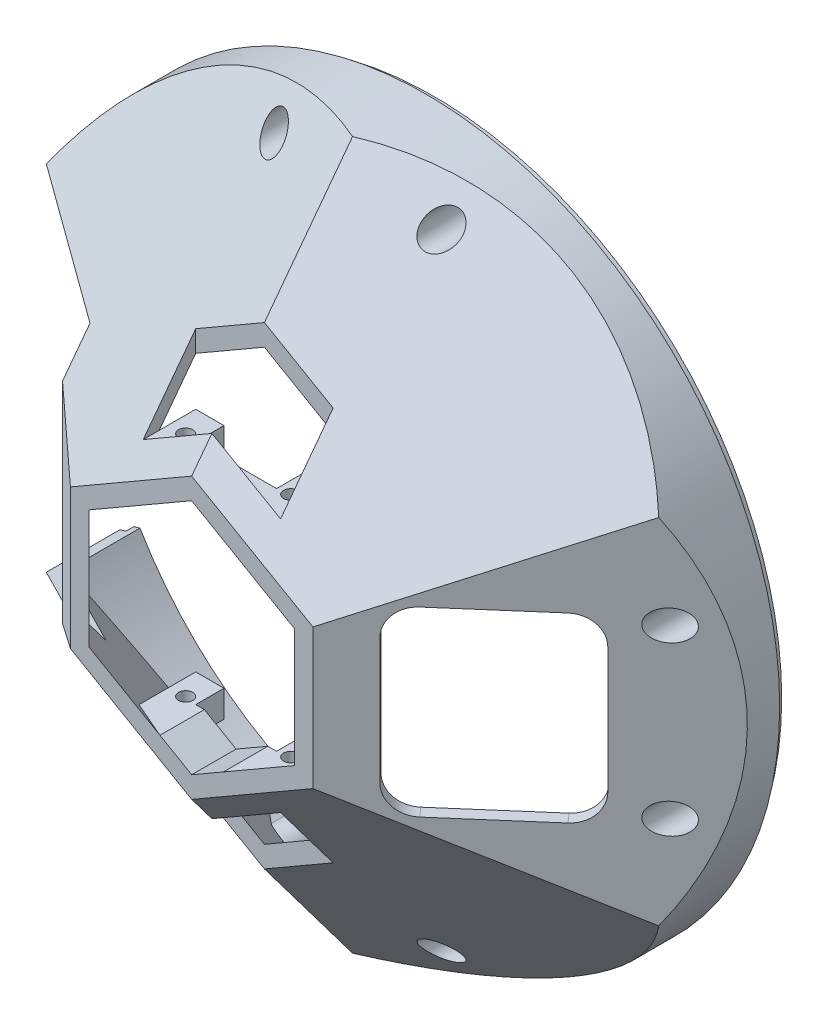
SolidWorks part; units mm, degrees
ref_plane "Front Plane" through (0, 0, 0) normal (0, 0, 1) x (1, 0, 0)
ref_plane "Top Plane" through (0, 0, 0) normal (0, 1, 0) x (1, 0, 0)
ref_plane "Right Plane" through (0, 0, 0) normal (1, 0, 0) x (0, 0, -1)
sketch "Sketch1" plane through (0, 0, 0) normal (0, 0, 1) x (1, 0, 0)
  circle A0 centre (0, 0) radius 87.5
  dimension "D1" = 175
extrude "Boss-Extrude1" add sketch "Sketch1" along normal blind 60
sketch "Sketch2" plane through (0, 0, 0) normal (0, 1, 0) x (1, 0, 0)
  line L0 (-73.4655, -109.9854) -> (-130.9655, -59.9854)
  line L1 (-73.4655, -109.9854) -> (-30, -60)
  line L2 (-130.9655, -59.9854) -> (-87.5, -10)
  line L3 (-30, -60) -> (-87.5, -10)
  line L4 (-73.4655, -109.9854) -> (-87.5, -10) construction
  line L5 (-130.9655, -59.9854) -> (-30, -60) construction
  line L7 (-87.5, 0) -> (-87.5, -60) construction
  line L8 (-87.5, -60) -> (87.5, -60) construction
  point P1 (-80.4828, -59.9927)
  dimension "D1" = 30
  dimension "D2" = 10
extrude "Cut-Extrude1" cut sketch "Sketch2" against normal through all and the other way through all
pattern_circular "CirPattern1" count 6 over 360 about axis through (0, 0, 0) along (0, 0, 1) of "Cut-Extrude1"
shell "Shell1" thickness 3 removed face at (87.5, 0, 0) removed face at (0, 0, 60)
sketch "Sketch3" plane through (0, 0, 0) normal (0, 0, -1) x (-1, 0, 0)
  circle A0 centre (0, 0) radius 87.5 construction
  circle A1 centre (0, 0) radius 87.5
  circle A2 centre (0, 0) radius 86
  dimension "D1" = 1.5
extrude "Cut-Extrude2" cut sketch "Sketch3" against normal blind 2
sketch "Sketch4" plane through (0, 0, 0) normal (0, 0, 1) x (1, 0, 0)
  line L8 (-45, 35) -> (-45, -35)
  line L9 (-30, -17.3205) -> (-30, 17.3205) construction
  line L10 (-75.7772, 43.75) -> (-45, 35)
  line L11 (-45, -35) -> (-75.7772, -43.75)
  line L12 (-45, 0) -> (0, 0) construction
  arc A1 (-75.7772, 43.75) -> (-75.7772, -43.75) centre (0, 0) ccw construction
  arc A2 (-75.7772, 43.75) -> (-75.7772, -43.75) centre (0, 0) ccw
  dimension "D1" = 15
  dimension "D2" = 70
extrude "Cut-Extrude3" cut sketch "Sketch4" along normal through all
sketch "Sketch5" plane through (0, 0, 0) normal (0, 0, 1) x (1, 0, 0)
  line L0 (0, 0) -> (-20.7055, 77.2741) construction
  line L1 (0, 84.5) -> (0, 29.3618) construction
  line L2 (-23.5083, 73.1335) -> (-31.3758, 78.459)
  line L3 (-16.208, 75.0896) -> (-12.0573, 83.6354)
  line L4 (-31.3758, 78.459) -> (-12.0573, 83.6354) construction
  line L5 (-21.7165, 81.0472) -> (-20.7055, 77.2741) construction
  arc A0 (-23.5083, 73.1335) -> (-16.208, 75.0896) centre (-20.7055, 77.2741) ccw
  arc A1 (-72.7982, -42.9031) -> (-72.7982, 42.9031) centre (0, 0) ccw construction
  arc A2 (0, 84.5) -> (-72.7982, 42.9031) centre (0, 0) ccw construction
  arc A3 (-12.0573, 83.6354) -> (-31.3758, 78.459) centre (0, 0) ccw
  dimension "D2" = 10
  dimension "D1" = 15
  dimension "D3" = 80
  dimension "D4" = 20
extrude "Boss-Extrude2" add sketch "Sketch5" along normal up to next
sketch "Sketch6" plane through (0, 0, 0) normal (0, 0, -1) x (-1, 0, 0)
  circle A0 centre (20.7055, 77.2741) radius 1.75
  dimension "D1" = 3.5
extrude "Cut-Extrude4" cut sketch "Sketch6" against normal through all
sketch "Sketch7" plane through (0, 0, 60) normal (0, 0, 1) x (1, 0, 0)
  circle A2 centre (-20.7055, 77.2741) radius 3.75
  circle A3 centre (-20.7055, 77.2741) radius 3.75
  dimension "D1" = 2
extrude "Cut-Extrude5" cut sketch "Sketch7" against normal blind 55
mirror "Mirror1" about plane through (0, 0, 0) normal (1, 0, 0) of "Cut-Extrude5", "Cut-Extrude4", "Boss-Extrude2"
pattern_circular "CirPattern2" count 3 every 90 about axis through (0, 0, 2) along (0, 0, -1) of "Mirror1"
sketch "Sketch8" plane through (42.6265, 0, 49.0205) normal (0.6562, 0, 0.7546) x (0.7546, 0, -0.6562)
  line L0 (0, 0) -> (15, 0) construction
  line L1 (2, 22.5) -> (28, 22.5)
  line L2 (-5, 15.5) -> (-5, -15.5)
  line L3 (2, -22.5) -> (28, -22.5)
  line L4 (35, 15.5) -> (35, -15.5)
  line L5 (-5, 22.5) -> (35, -22.5) construction
  line L6 (-5, -22.5) -> (35, 22.5) construction
  arc A0 (-5, -15.5) -> (2, -22.5) centre (2, -15.5) ccw
  arc A1 (28, -22.5) -> (35, -15.5) centre (28, -15.5) ccw
  arc A2 (28, 22.5) -> (35, 15.5) centre (28, 15.5) cw
  arc A3 (2, 22.5) -> (-5, 15.5) centre (2, 15.5) ccw
  point P0 (15, 0)
  dimension "D4" = 7
  dimension "D1" = 45
  dimension "D2" = 40
  dimension "D3" = 15
extrude "Cut-Extrude6" cut sketch "Sketch8" against normal through all
sketch "Sketch10" plane through (0, 0, 0) normal (0, 1, 0) x (1, 0, 0)
  line L0 (0, -20.1937) -> (0, -60) construction
  line L1 (-17, -42) -> (17, -42)
  line L2 (-17, -42) -> (-17, -55)
  line L3 (-17, -55) -> (17, -55)
  line L4 (17, -42) -> (17, -55)
  line L5 (-17, -42) -> (17, -55) construction
  line L6 (-17, -55) -> (17, -42) construction
  line L7 (0, -48.5) -> (0, 0) construction
  line L8 (0, -60) -> (30, -60) construction
  point P0 (0, -48.5)
  dimension "D1" = 13
  dimension "D2" = 34
  dimension "D3" = 5
extrude "Cut-Extrude8" cut sketch "Sketch10" against normal through all
sketch "Sketch12" plane through (0, 0, 42) normal (0, 0, 1) x (1, 0, 0)
  line L0 (17, -31.4656) -> (17, -48.7284) construction
  line L1 (-17, -31.4656) -> (17, -31.4656)
  line L2 (-17, -31.4656) -> (-17, -24.8261)
  line L4 (17, -31.4656) -> (17, -24.8261)
  line L5 (0, -41.2805) -> (17, -31.4656) construction
  line L6 (30, -17.3205) -> (0, -34.641) construction
  line L7 (0, -34.641) -> (-30, -17.3205) construction
  line L8 (-17, -24.8261) -> (-7.8561, -24.8261)
  line L9 (0, -29.3618) -> (-25.4281, -14.6809) construction
  line L10 (-7.8561, -24.8261) -> (0, -29.3618)
  line L11 (0, -29.3618) -> (7.8561, -24.8261)
  line L12 (25.4281, -14.6809) -> (0, -29.3618) construction
  line L13 (7.8561, -24.8261) -> (17, -24.8261)
extrude "Boss-Extrude4" add sketch "Sketch12" along normal up to next
sketch "Sketch13" plane through (0, -31.4656, 0) normal (0, -1, 0) x (1, 0, 0)
  line L0 (0, 42) -> (-17, 42) construction
  line L1 (-10, 42) -> (10, 42)
  line L2 (-10, 42) -> (-10, 49)
  line L3 (-10, 49) -> (10, 49)
  line L4 (10, 42) -> (10, 49)
  line L5 (0, 49) -> (0, 60) construction
  line L6 (-13, 48.5) -> (-17, 48.5) construction
  line L9 (-13, 48.5) -> (13, 48.5) construction
  line L10 (-17, 42) -> (-17, 55) construction
  line L11 (13, 48.5) -> (17, 48.5) construction
  line L12 (17, 55) -> (17, 42) construction
  circle A0 centre (-13, 48.5) radius 1.75
  circle A1 centre (13, 48.5) radius 1.75
  point P9 (0, 48.5)
  dimension "D4" = 3.5
  dimension "D1" = 7
  dimension "D2" = 20
  dimension "D3" = 26
extrude "Cut-Extrude9" cut sketch "Sketch13" against normal blind 8
mirror "Mirror2" about plane through (0, 0, 0) normal (0, 1, 0) of "Cut-Extrude9", "Boss-Extrude4", "Cut-Extrude8"
